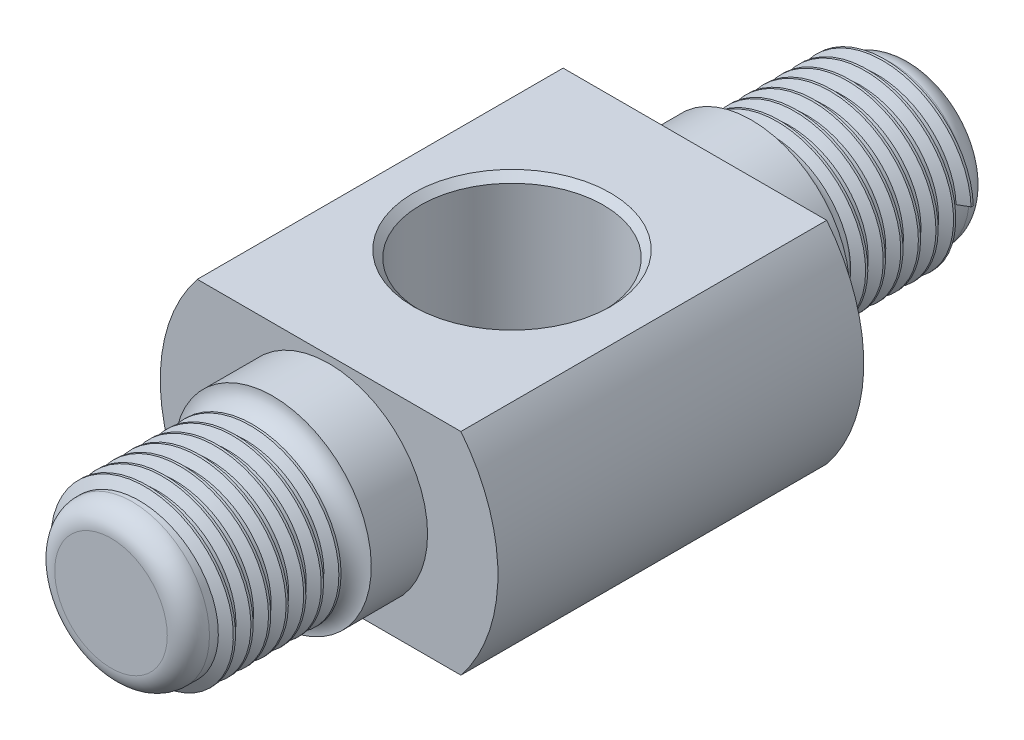
SolidWorks part; units mm, degrees
ref_plane "Front Plane" through (0, 0, 0) normal (0, 0, 1) x (1, 0, 0)
ref_plane "Top Plane" through (0, 0, 0) normal (0, 1, 0) x (1, 0, 0)
ref_plane "Right Plane" through (0, 0, 0) normal (1, 0, 0) x (0, 0, -1)
sketch "Sketch1" plane through (0, 0, 0) normal (0, 0, 1) x (1, 0, 0)
  line L1 (-9.3675, -7.5) -> (9.3675, -7.5)
  line L3 (-9.3675, 7.5) -> (9.3675, 7.5)
  arc A0 (-9.3675, 7.5) -> (-9.3675, -7.5) centre (0, 0) ccw
  arc A1 (9.3675, 7.5) -> (9.3675, -7.5) centre (0, 0) cw
  point P0 (0, 0)
  dimension "D3" = 12
  dimension "D4" = 12
  dimension "D5" = 18.735
  dimension "D6" = 18.735
  dimension "D7" = 7.5
extrude "Boss-Extrude1" add sketch "Sketch1" along normal blind 26
sketch "Sketch8" plane through (0, 7.5, 0) normal (0, 1, 0) x (1, 0, 0)
  line L0 (9.3675, 0) -> (-9.3675, -26)
  point P4 (0, -13)
hole_wizard "Ø13.0 (13) Diameter Hole1" positions "3DSketch4" profile "Sketch9" hole size "Ø13.0" standard "ISO" end condition through all
sketch3d "3DSketch4"
  point P0 (0, 7.5, 13)
sketch "Sketch9" plane through (0, 7.5, 13) normal (1, 0, 0) x (0, 0, 1)
  line L0 (0, 0) -> (0, 15)
  line L1 (0, 15) -> (6.5, 15)
  line L2 (6.5, 15) -> (6.5, 0)
  line L5 (6.5, 0) -> (0, 0)
  line L11 (0, -6.35) -> (0, 107.95) construction
  dimension "Thru Hole Dia." = 13
  dimension "Thru Hole Depth" = 15
chamfer "Chamfer2" distance 0.5 angle 45 2 edges at (0, -7.5, 19.5) (0, 7.5, 19.5)
sketch "Sketch25" plane through (0, 0, 0) normal (0, 0, -1) x (-1, 0, 0)
  circle A0 centre (0, 0) radius 7
  dimension "D1" = 14
extrude "Boss-Extrude2" add sketch "Sketch25" along normal blind 4
sketch "Sketch26" plane through (0, 0, -4) normal (0, 0, -1) x (-1, 0, 0)
  circle A0 centre (0, 0) radius 5.5
  dimension "D1" = 11
extrude "Boss-Extrude3" add sketch "Sketch26" along normal blind 11.5
fillet "Fillet1" radius 1.5 1 edges at (-5.5, 0, -4)
fillet "Fillet2" radius 1.5 1 edges at (-5.5, 0, -15.5)
thread "Thread2" pitch 1.25 method extrude profile "Thread Profile2" start angle 0, offset 0, length 0, pitch 1.25, diameter 11
ref_plane "Plane2" through (5.5, 0, -14) normal (0, -1, 0) x (1, 0, 0)
sketch "Thread Profile2" plane through (5.5, 0, -14) normal (0, -1, 0) x (1, 0, 0)
  line L0 (0, 0) -> (0, 1.25) construction
  line L1 (0, 0) -> (0.6766, 0.3906)
  line L2 (0.6766, 0.3906) -> (0.6766, 0.5469)
  line L3 (0.6766, 0.5469) -> (0, 0.9375)
  line L4 (0.6766, 0.4687) -> (0, 0.4687) construction
  line L11 (0, 0) -> (0, 0.9375)
  point P2 (0, 0)
  dimension "Pitch" = 1.25
  dimension "Profile_Angle" = 60
  dimension "Profile_Land" = 0.1562
  dimension "Profile_Height" = 0.6766
ref_plane "Plane3" through (0, 0, 13) normal (0, 0, -1) x (-1, 0, 0)
mirror "Mirror2" about plane through (0, 0, 13) normal (0, 0, -1) of "Fillet2", "Fillet1", "Boss-Extrude3", "Boss-Extrude2"
thread "Thread3" pitch 1.25 method extrude profile "Thread Profile3" start angle 0, offset 0, length 0, pitch 1.25, diameter 11
ref_plane "Plane4" through (-5.5, 0, 40) normal (0, -1, 0) x (-1, 0, 0)
sketch "Thread Profile3" plane through (-5.5, 0, 40) normal (0, -1, 0) x (-1, 0, 0)
  line L0 (0, 0) -> (0, 1.25) construction
  line L1 (0, 0) -> (0.6766, 0.3906)
  line L2 (0.6766, 0.3906) -> (0.6766, 0.5469)
  line L3 (0.6766, 0.5469) -> (0, 0.9375)
  line L4 (0.6766, 0.4687) -> (0, 0.4687) construction
  line L11 (0, 0) -> (0, 0.9375)
  point P2 (0, 0)
  dimension "Pitch" = 1.25
  dimension "Profile_Angle" = 60
  dimension "Profile_Land" = 0.1562
  dimension "Profile_Height" = 0.6766
